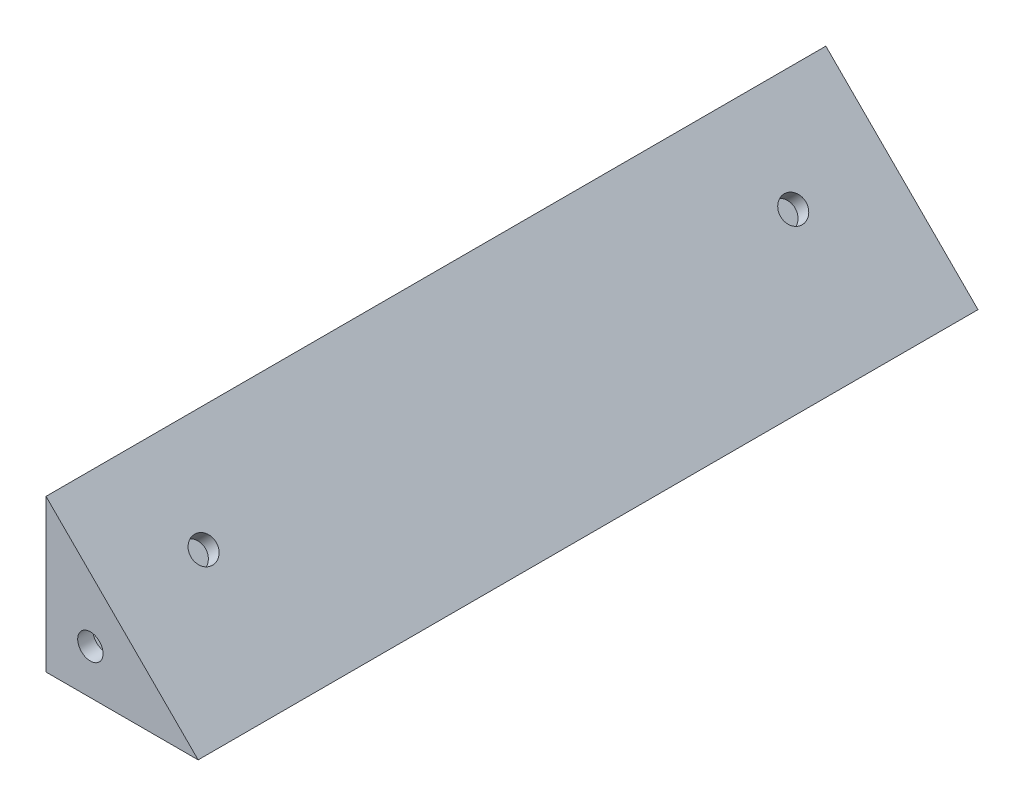
SolidWorks part; units mm, degrees
ref_plane "Front Plane" through (0, 0, 0) normal (0, 0, 1) x (1, 0, 0)
ref_plane "Top Plane" through (0, 0, 0) normal (0, 1, 0) x (1, 0, 0)
ref_plane "Right Plane" through (0, 0, 0) normal (1, 0, 0) x (0, 0, -1)
sketch "Sketch1" plane through (0, 0, 0) normal (0, 0, 1) x (1, 0, 0)
  line L0 (0, 12) -> (12, 0)
  line L1 (0, 0) -> (12, 0)
  line L2 (0, 0) -> (0, 12)
  line L3 (0, 12) -> (12, 12)
  line L4 (12, 0) -> (12, 12)
  line L5 (6.2884, 4.2471) -> (10.5355, 0)
  line L12 (6.2884, 4.2471) -> (4.2471, 6.2884)
  line L13 (4.2471, 6.2884) -> (1.4588, 5.5412)
  line L14 (1.4588, 5.5412) -> (0.7116, 2.7529)
  line L15 (0.7116, 2.7529) -> (2.7529, 0.7116)
  line L16 (2.7529, 0.7116) -> (5.5412, 1.4588)
  line L17 (5.5412, 1.4588) -> (6.2884, 4.2471)
  line L18 (0, 0) -> (3.5, 0)
  line L19 (0, 0) -> (0, 3.5)
  line L20 (0, 3.5) -> (3.5, 3.5)
  line L21 (3.5, 0) -> (3.5, 3.5)
  line L22 (0, 0) -> (7, 0)
  line L23 (0, 0) -> (0, 3.3869)
  line L26 (2.7529, 0.7116) -> (3.4645, 0)
  line L28 (0, 0) -> (12, 0)
  line L29 (0, 0) -> (0, -2.2374)
  line L30 (0, -2.2374) -> (12, -2.2374)
  line L31 (12, 0) -> (12, -2.2374)
  circle A0 centre (3.5, 3.5) radius 1
  circle A1 centre (3.5, 3.5) radius 2.5 construction
  dimension "D1" = 3.5
  dimension "D3" = 5
  dimension "D4" = 12
  dimension "D2" = 12
  dimension "D5" = 3.5
extrude "Boss-Extrude1" add sketch "Sketch1" along normal blind 61.5 contours L21 L1 L5 L17 L16 | L16 L21 L20 L14 L15 | L26 L15 L14 L20 L19 L2 L1 | L16 L26 L22 L21 | L2 L20 L14 L13 L12 L5 L1 L0 | A0 L21 L16 L17 L12 L13 L14 L20 | L20 A0 L21 | L21 A0 L20 region at (3.6782, 6.2001, 0) region at (1.1201, 1.2713, 0) region at (6.879, 1.2904, 0) region at (2.2612, 2.2612, 0) region at (1.2587, 4.5009, 0) region at (3.6415, 3.6415, 0) region at (3.0756, 3.0756, 0) region at (3.2505, 0.5303, 0)
extrude "Cut-Extrude1" cut sketch "Sketch1<4>" along normal blind 3.2 contours L21 L16 L17 L12 L13 L14 L20 | L16 L21 L20 L14 L15 | L21 L1 L5 L17 L16 | L16 L26 L22 L21 | A0 region at (6.879, 1.2904, 0) region at (2.2612, 2.2612, 0) region at (1.2587, 4.5009, 0) region at (3.2505, 0.5303, 0)
sketch "Sketch1<4>" plane through (0, 0, 0) normal (0, 0, 1) x (1, 0, 0) same geometry as "Sketch1"
extrude "Boss-Extrude2" add sketch "Sketch1<5>" along normal blind 1.2 contours L21 L16 L17 L12 L13 L14 L20 | L16 L21 L20 L14 L15 | L21 L1 L5 L17 L16 | L16 L26 L22 L21 region at (6.879, 1.2904, 0) region at (2.2612, 2.2612, 0) region at (1.2587, 4.5009, 0) region at (3.2505, 0.5303, 0)
sketch "Sketch1<5>" plane through (0, 0, 0) normal (0, 0, 1) x (1, 0, 0) same geometry as "Sketch1"
sketch "Sketch2" plane through (0, 0, 61.5) normal (0, 0, 1) x (1, 0, 0)
  line L0 (6.2884, 4.2471) -> (10.5355, 0)
  line L1 (6.2884, 4.2471) -> (4.2471, 6.2884)
  line L2 (4.2471, 6.2884) -> (1.4588, 5.5412)
  line L3 (1.4588, 5.5412) -> (0.7116, 2.7529)
  line L4 (0.7116, 2.7529) -> (2.7529, 0.7116)
  line L5 (2.7529, 0.7116) -> (5.5412, 1.4588)
  line L6 (5.5412, 1.4588) -> (6.2884, 4.2471)
  line L7 (2.7529, 0.7116) -> (3.4645, 0)
  line L8 (3.4645, 0) -> (10.5355, 0)
  circle A0 centre (3.5, 3.5) radius 2.5 construction
  circle A1 centre (3.5, 3.5) radius 1
  line M8 (0, 0) -> (12, 0)
extrude "Cut-Extrude2" cut sketch "Sketch2" against normal blind 3.2 contours L5 L6 L1 L2 L3 L4 | L5 L7 L0 L6 M8 | A1 region at (5.8386, 2.8734, 61.5) region at (6.7869, 1.2711, 61.5)
extrude "Boss-Extrude3" add sketch "Sketch2<4>" against normal blind 1.2 contours L5 L6 L1 L2 L3 L4 | L5 L7 L0 L6 M8 region at (5.8386, 2.8734, 61.5) region at (6.7869, 1.2711, 61.5)
sketch "Sketch2<4>" plane through (0, 0, 61.5) normal (0, 0, 1) x (1, 0, 0) same geometry as "Sketch2"
sketch "Sketch4" plane through (6, 6, 0) normal (0.7071, 0.7071, 0) x (0, 0, -1)
  line L0 (0, 0) -> (0, -8.4853) construction
  line L1 (0, -8.4853) -> (-5, -8.4853)
  line L2 (0, -8.4853) -> (0, 8.4853)
  line L3 (0, 8.4853) -> (-5, 8.4853)
  line L4 (-5, -8.4853) -> (-5, 8.4853)
  line L5 (0, 8.4853) -> (0, -8.4853) construction
  line L6 (-61.5, 8.4853) -> (0, 8.4853) construction
  line L7 (-5, 0.0713) -> (-5, -8.4853)
  line L8 (-7.5, 4.4015) -> (-10, 2.9581)
  line L9 (-10, 2.9581) -> (-10, 0.0713)
  line L10 (-10, 0.0713) -> (-7.5, -1.372)
  line L11 (-7.5, -1.372) -> (-5, 0.0713)
  line L12 (-5, 0.0713) -> (-5, 2.9581)
  line L13 (-5, 2.9581) -> (-7.5, 4.4015)
  line L14 (-61.5, -8.4853) -> (0, -8.4853) construction
  line L15 (-10, 0.0713) -> (-10, -8.4853)
  line L16 (-51.5, 0.0713) -> (-51.5, -8.4853)
  line L17 (-7.5, 1.5147) -> (0, 1.5147)
  line L18 (-7.5, 1.5147) -> (-7.5, -8.4853)
  line L19 (-7.5, -8.4853) -> (0, -8.4853)
  line L20 (0, 1.5147) -> (0, -8.4853)
  line L21 (-61.5, -8.4853) -> (-54, -8.4853)
  line L22 (-61.5, -8.4853) -> (-61.5, 1.5147)
  line L23 (-61.5, 1.5147) -> (-54, 1.5147)
  line L24 (-54, -8.4853) -> (-54, 1.5147)
  line L25 (-54, 4.4015) -> (-56.5, 2.9581)
  line L26 (-56.5, 2.9581) -> (-56.5, 0.0713)
  line L27 (-56.5, 0.0713) -> (-54, -1.372)
  line L28 (-54, -1.372) -> (-51.5, 0.0713)
  line L29 (-51.5, 0.0713) -> (-51.5, 2.9581)
  line L30 (-51.5, 2.9581) -> (-54, 4.4015)
  line L31 (-56.5, 0.0713) -> (-56.5, -8.4853)
  circle A0 centre (-7.5, 1.5147) radius 2.5 construction
  circle A1 centre (-54, 1.5147) radius 2.5 construction
  circle A2 centre (-54, 1.5147) radius 1
  circle A3 centre (-7.5, 1.5147) radius 1
  line M28 (-61.5, -8.4853) -> (0, -8.4853)
  dimension "D2" = 5
  dimension "D7" = 5
  dimension "D8" = 2
  dimension "D1" = 5
  dimension "D3" = 7.5
  dimension "D4" = 10
  dimension "D5" = 7.5
  dimension "D6" = 10
extrude "Cut-Extrude3" cut sketch "Sketch4" against normal blind 3.2 contours A2 L24 L28 L29 L30 L25 L26 L23 | A2 L23 L26 L27 L24 | L27 L31 L21 L24 | L24 A2 L23 | L28 L24 L16 M28 | L23 A2 L24 | L11 L18 L4 M28 | L18 L10 L15 M28 | A3 L17 L12 L13 L8 L9 L10 L18 | A3 L18 L11 L4 L17 | L17 A3 L18 | L18 A3 L17 region at (9.2221, 2.7779, 52.7116) region at (9.2221, 2.7779, 6.2116) region at (5.8065, 6.1935, 6.2723) region at (9.2221, 2.7779, 8.7884) region at (4.8749, 7.1251, 5.75) region at (5.229, 6.771, 7.0756) region at (4.8289, 7.1711, 7.6415) region at (6.4131, 5.5869, 52.7882) region at (9.2221, 2.7779, 55.2884) region at (5.8065, 6.1935, 55.2277) region at (5.229, 6.771, 54.4244) region at (4.8289, 7.1711, 53.8585)
extrude "Boss-Extrude4" add sketch "Sketch4<3>" against normal blind 1.2 contours A2 L24 L28 L29 L30 L25 L26 L23 | A2 L23 L26 L27 L24 | L28 L24 L16 M28 | L27 L31 L21 L24 | A3 L17 L12 L13 L8 L9 L10 L18 | A3 L18 L11 L4 L17 | L11 L18 L4 M28 | L18 L10 L15 M28 region at (9.2221, 2.7779, 52.7116) region at (9.2221, 2.7779, 6.2116) region at (5.8065, 6.1935, 6.2723) region at (9.2221, 2.7779, 8.7884) region at (4.8749, 7.1251, 5.75) region at (6.4131, 5.5869, 52.7882) region at (9.2221, 2.7779, 55.2884) region at (5.8065, 6.1935, 55.2277)
sketch "Sketch4<3>" plane through (6, 6, 0) normal (0.7071, 0.7071, 0) x (0, 0, -1) same geometry as "Sketch4"
extrude "Cut-Extrude4" cut sketch "Sketch1<6>" along normal through all contours L31 L1 L22 L29 L30 region at (6, -1.1187, 0)
sketch "Sketch1<6>" plane through (0, 0, 0) normal (0, 0, 1) x (1, 0, 0) same geometry as "Sketch1"
